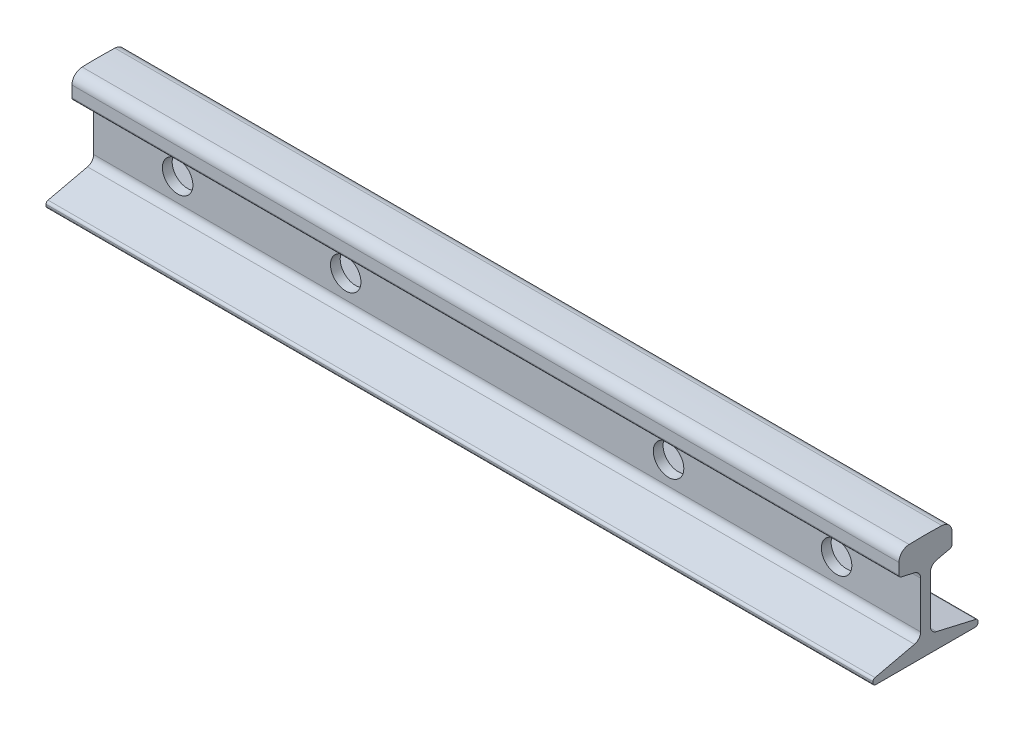
SolidWorks part; units mm, degrees
ref_plane "Front" through (0, 0, 0) normal (0, 0, 1) x (1, 0, 0)
ref_plane "Top" through (0, 0, 0) normal (0, 1, 0) x (1, 0, 0)
ref_plane "Right" through (0, 0, 0) normal (1, 0, 0) x (0, 0, -1)
sketch "Sketch1" plane through (0, 0, 0) normal (1, 0, 0) x (0, 0, -1)
  line L1 (16.05, 63.0771) -> (16.05, 49.0444)
  line L2 (16.05, 49.0444) -> (2.95, 46.02)
  line L3 (2.95, 46.02) -> (2.95, 10.3)
  line L4 (2.95, 10.3) -> (31.75, 3.651)
  line L5 (31.75, 3.651) -> (31.75, 0)
  line L6 (31.75, 0) -> (-31.75, 0)
  line L7 (0, 0) -> (0, 92.0717) construction
  line L8 (-31.75, 3.651) -> (-31.75, 0)
  line L9 (-2.95, 10.3) -> (-31.75, 3.651)
  line L10 (-2.95, 46.02) -> (-2.95, 10.3)
  line L11 (-16.05, 49.0444) -> (-2.95, 46.02)
  line L12 (-16.05, 63.0771) -> (-16.05, 49.0444)
  arc A0 (-16.05, 63.0771) -> (16.05, 63.0771) centre (0, -241.3) cw
  dimension "D5" = 304.8
  dimension "D6" = 63.5
  dimension "D1" = 63.5
  dimension "D2" = 13
  dimension "D3" = 5.9
  dimension "D4" = 10.3
  dimension "D7" = 32.1
  dimension "D8" = 35.72
  dimension "D9" = 13
extrude "Base" add sketch "Sketch1" along normal blind 500
fillet "Fillet1" radius 6.35 2 edges at (250, 63.0771, -16.05) (250, 63.0771, 16.05)
fillet "Fillet2" radius 4.76 4 edges at (250, 46.02, -2.95) (250, 10.3, -2.95) (250, 46.02, 2.95) (250, 10.3, 2.95)
fillet "Fillet3" radius 1.59 6 edges at (250, 49.0444, 16.05) (250, 0, -31.75) (250, 3.651, -31.75) (250, 0, 31.75) (250, 3.651, 31.75) (250, 49.0444, -16.05) tangent propagation no
sketch "Sketch2" plane through (416.8909, -3.4733, 2.95) normal (0, 0, 1) x (1, 0, 0)
  line L0 (-416.8909, 45.707) -> (-416.8909, 17.5595) construction
  line L1 (-416.8909, 66.8122) -> (83.1091, 66.8122) construction
  line L3 (83.1091, 45.707) -> (83.1091, 17.5595) construction
  circle A0 centre (-366.0945, 31.4722) radius 9.2173
  circle A1 centre (-264.4945, 31.4722) radius 9.2173
  circle A2 centre (-69.2873, 31.4722) radius 9.2173
  circle A3 centre (32.3127, 31.4722) radius 9.2173
  dimension "D3" = 18.4345
  dimension "D4" = 101.6
  dimension "D6" = 101.6
  dimension "D5" = 50.7964
  dimension "D1" = 35.34
  dimension "D2" = 50.7964
extrude "Cut-Extrude1" cut sketch "Sketch2" against normal through all
equation "\"D5@Sketch2\" = \"D2@Sketch2\""
equation "\"D6@Sketch2\" = \"D4@Sketch2\""
